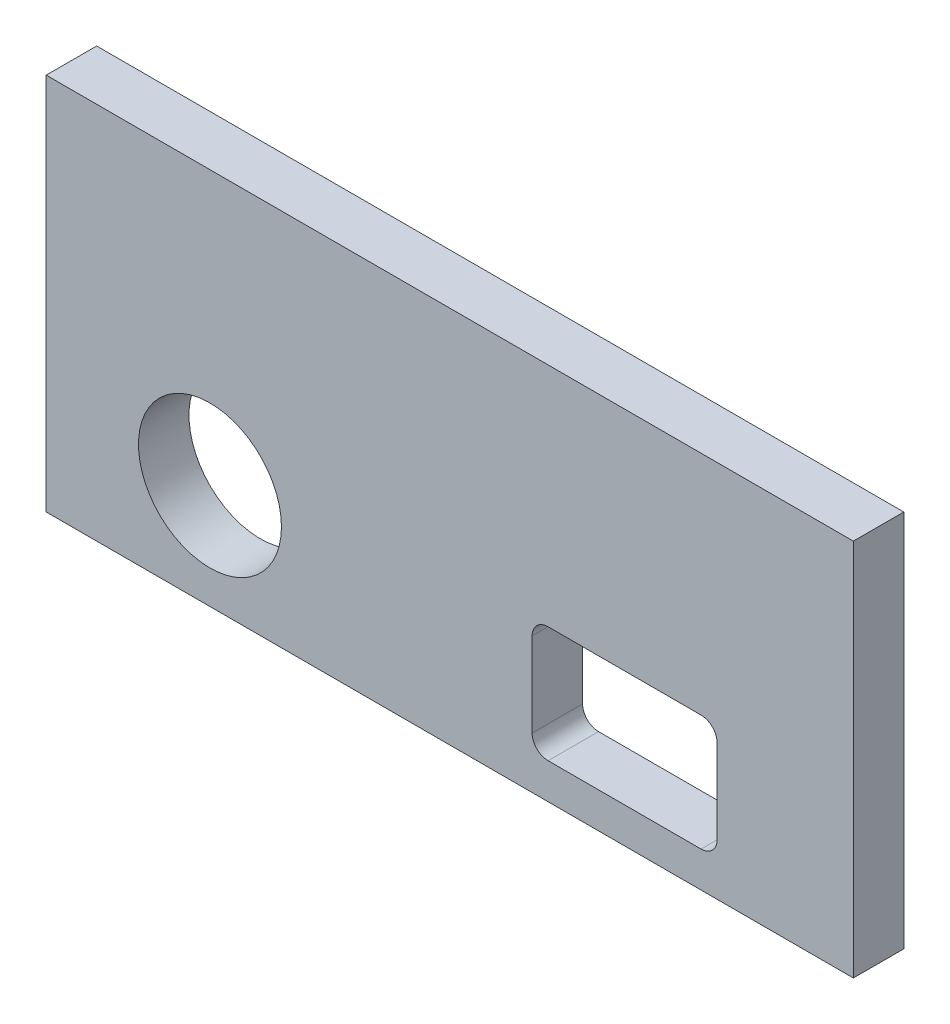
SolidWorks part; units mm, degrees
material "Acrylic (Medium-high impact)"
ref_plane "Front Plane" through (0, 0, 0) normal (0, 0, 1) x (1, 0, 0)
ref_plane "Top Plane" through (0, 0, 0) normal (0, 1, 0) x (1, 0, 0)
ref_plane "Right Plane" through (0, 0, 0) normal (1, 0, 0) x (0, 0, -1)
sketch "Sketch1" plane through (0, 0, 74.2805) normal (0, 0, 1) x (1, 0, 0)
  line L1 (8.9215, 47.1718) -> (56.9215, 47.1718)
  line L2 (8.9215, 47.1718) -> (8.9215, 24.6718)
  line L3 (8.9215, 24.6718) -> (56.9215, 24.6718)
  line L4 (56.9215, 47.1718) -> (56.9215, 24.6718)
  line L53 (37.8186, 32.7359) -> (37.8186, 27.7359)
  line L54 (38.7686, 26.7859) -> (47.8686, 26.7859)
  line L55 (48.8186, 27.7359) -> (48.8186, 32.7359)
  line L56 (47.8686, 33.6859) -> (38.7686, 33.6859)
  circle A28 centre (18.6608, 30.9068) radius 4.25
  arc A29 (37.8186, 27.7359) -> (38.7686, 26.7859) centre (38.7686, 27.7359) ccw
  arc A30 (47.8686, 26.7859) -> (48.8186, 27.7359) centre (47.8686, 27.7359) ccw
  arc A31 (48.8186, 32.7359) -> (47.8686, 33.6859) centre (47.8686, 32.7359) ccw
  arc A32 (38.7686, 33.6859) -> (37.8186, 32.7359) centre (38.7686, 32.7359) ccw
extrude "Boss-Extrude1" add sketch "Sketch1" along normal blind 3 from offset 0.25
